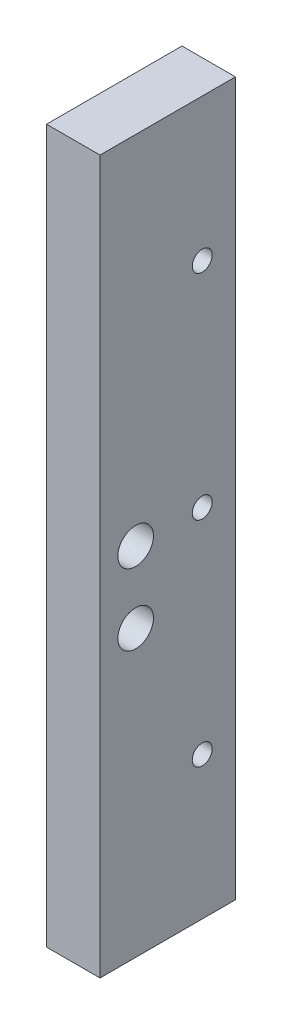
SolidWorks part; units mm, degrees
ref_plane "Front Plane" through (0, 0, 0) normal (0, 0, 1) x (1, 0, 0)
ref_plane "Top Plane" through (0, 0, 0) normal (0, 1, 0) x (1, 0, 0)
ref_plane "Right Plane" through (0, 0, 0) normal (1, 0, 0) x (0, 0, -1)
sketch "Sketch1" plane through (0, 0, 0) normal (0, 0, 1) x (1, 0, 0)
  line L1 (0, 0) -> (9.525, 0)
  line L2 (0, 0) -> (0, 127)
  line L3 (0, 127) -> (9.525, 127)
  line L4 (9.525, 0) -> (9.525, 127)
  dimension "D1" = 9.525
  dimension "D2" = 127
extrude "Boss-Extrude1" add sketch "Sketch1" along normal blind 24.13
sketch "Sketch2" plane through (0, 0, 0) normal (-1, 0, 0) x (0, 0, 1)
  line L0 (5.9182, 127) -> (5.9182, 0) construction
  line L1 (24.13, 127) -> (0, 127) construction
  line L2 (24.13, 0) -> (0, 0) construction
  line L3 (0, 127) -> (0, 0) construction
  circle A0 centre (5.9182, 101.6) radius 1.778
  circle A1 centre (5.9182, 63.5) radius 1.778
  circle A2 centre (5.9182, 25.4) radius 1.778
  dimension "D2" = 3.556
  dimension "D3" = 25.4
  dimension "D1" = 5.9182
  dimension "D4" = 38.1
  dimension "D5" = 38.1
extrude "Cut-Extrude1" cut sketch "Sketch2" against normal through all
sketch "Sketch3" plane through (9.525, 0, 0) normal (1, 0, 0) x (0, 0, -1)
  line L0 (-17.78, 127) -> (-17.78, 0) construction
  line L1 (-24.13, 127) -> (0, 127) construction
  line L2 (-24.13, 0) -> (0, 0) construction
  line L3 (-24.13, 0) -> (-24.13, 127) construction
  circle A0 centre (-17.78, 63.5) radius 3.175
  circle A1 centre (-17.78, 50.8) radius 3.175
  dimension "D1" = 6.35
  dimension "D2" = 6.35
  dimension "D3" = 12.7
  dimension "D4" = 6.35
  dimension "D5" = 63.5
extrude "Cut-Extrude2" cut sketch "Sketch3" against normal blind 38.1
